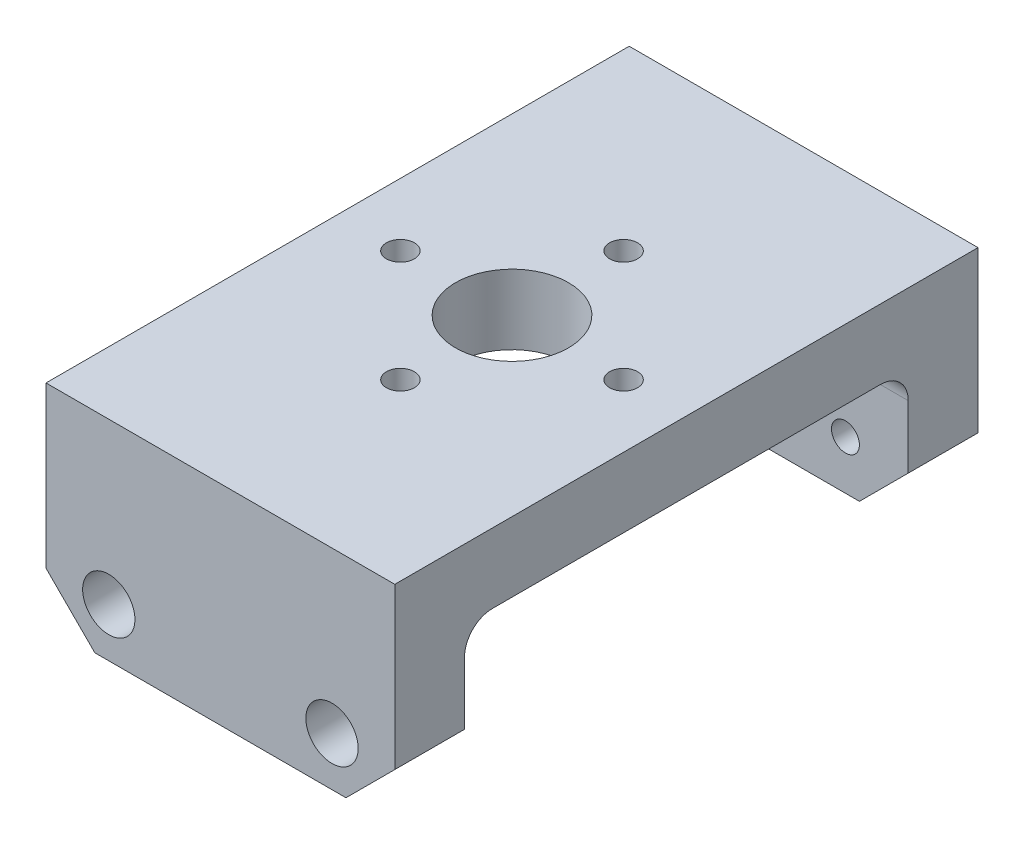
SolidWorks part; units mm, degrees
ref_plane "Front Plane" through (0, 0, 0) normal (0, 0, 1) x (1, 0, 0)
ref_plane "Top Plane" through (0, 0, 0) normal (0, 1, 0) x (1, 0, 0)
ref_plane "Right Plane" through (0, 0, 0) normal (1, 0, 0) x (0, 0, -1)
sketch "Sketch1" plane through (0, 0, 0) normal (0, 0, 1) x (1, 0, 0)
  line L1 (0, 0) -> (25, 0)
  line L2 (0, 0) -> (0, 15)
  line L3 (0, 15) -> (25, 15)
  line L4 (25, 0) -> (25, 15)
  circle A0 centre (4.5, 3.5) radius 1
  circle A1 centre (20.5, 3.5) radius 1
  dimension "D3" = 2
  dimension "D4" = 2
  dimension "D1" = 15
  dimension "D2" = 25
  dimension "D5" = 16
  dimension "D6" = 3.5
  dimension "D7" = 3.5
  dimension "D8" = 4.5
extrude "Boss-Extrude1" add sketch "Sketch1" along normal blind 5
sketch "Sketch2" plane through (0, 0, 0) normal (0, 0, -1) x (-1, 0, 0)
  circle A0 centre (-20.5, 3.5) radius 1.875
  circle A1 centre (-4.5, 3.5) radius 1.875
  dimension "D1" = 3.75
  dimension "D2" = 3.75
extrude "Cut-Extrude1" cut sketch "Sketch2" against normal blind 3.3
sketch "Sketch3" plane through (0, 0, 0) normal (0, 0, -1) x (-1, 0, 0)
  line L0 (0, 0) -> (-3.5, 0)
  line L1 (0, 0) -> (-25, 0) construction
  line L2 (-3.5, 0) -> (0, 3.5)
  line L3 (0, 15) -> (0, 0) construction
  line L4 (0, 3.5) -> (0, 0)
  line L5 (-21.5, 0) -> (-25, 0)
  line L6 (-25, 0) -> (-25, 3.5)
  line L7 (-25, 0) -> (-25, 15) construction
  line L8 (-25, 3.5) -> (-21.5, 0)
  dimension "D1" = 3.5
  dimension "D2" = 3.5
  dimension "D3" = 3.5
  dimension "D4" = 3.5
extrude "Cut-Extrude2" cut sketch "Sketch3" against normal through all
ref_plane "Plane1" through (0, 0, 20.9) normal (0, 0, 1) x (1, 0, 0)
mirror "Mirror5" about plane through (0, 0, 20.9) normal (0, 0, 1) of bodies 103
sketch "Sketch4" plane through (0, 0, 36.8) normal (0, 0, -1) x (-1, 0, 0)
  line L0 (0, 15) -> (0, 3.5) construction
  line L1 (-25, 15) -> (0, 15)
  line L2 (-25, 15) -> (-25, 10)
  line L3 (-25, 10) -> (0, 10)
  line L4 (0, 15) -> (0, 10)
  dimension "D1" = 5
extrude "Boss-Extrude2" add sketch "Sketch4" along normal up to next
sketch "Sketch5" plane through (0, 10, 0) normal (0, -1, 0) x (1, 0, 0)
  line L0 (25, 20.9) -> (0, 20.9) construction
  line L1 (25, 5) -> (25, 36.8) construction
  line L2 (12.5, 36.8) -> (12.5, 5) construction
  line L3 (25, 36.8) -> (0, 36.8) construction
  line L4 (25, 5) -> (0, 5) construction
  circle A0 centre (20.5, 20.9) radius 1
  dimension "D1" = 2
  dimension "D2" = 8
extrude "Cut-Extrude3" cut sketch "Sketch5" against normal through all
sketch "Sketch6" plane through (0, 10, 0) normal (0, -1, 0) x (-1, 0, 0)
  line L0 (-12.5, -36.8) -> (-12.5, -5) construction
  line L1 (-25, -36.8) -> (0, -36.8) construction
  line L2 (-25, -5) -> (0, -5) construction
  line L3 (-25, -20.9) -> (0, -20.9) construction
  line L4 (-25, -5) -> (-25, -36.8) construction
  line L5 (0, -5) -> (0, -36.8) construction
sketch "Sketch8" plane through (0, 10, 0) normal (0, -1, 0) x (1, 0, 0)
  circle A0 centre (20.5, 20.9) radius 1.875
  dimension "D1" = 3.75
extrude "Cut-Extrude4" cut sketch "Sketch8" against normal blind 1.25
ref_plane "Plane2" through (12.5, 0, 0) normal (1, 0, 0) x (0, 0, -1)
ref_axis "Axis1" through (12.5, -0.75, 20.9) along (0, 1, 0)
pattern_circular "CirPattern1" count 4 over 360 about axis through (12.5, -0.75, 20.9) along (0, 1, 0) of "Cut-Extrude3", "Cut-Extrude4"
sketch "Sketch9" plane through (0, 10, 0) normal (0, -1, 0) x (1, 0, 0)
  line L0 (25, 20.9) -> (0, 20.9) construction
  line L1 (25, 5) -> (25, 36.8) construction
  line L2 (12.5, 36.8) -> (12.5, 5) construction
  circle A0 centre (12.5, 20.9) radius 4.05
  dimension "D1" = 8.1
extrude "Cut-Extrude5" cut sketch "Sketch9" against normal through all
fillet "Fillet1" radius 2 1 edges
fillet "Fillet2" radius 2 1 edges
